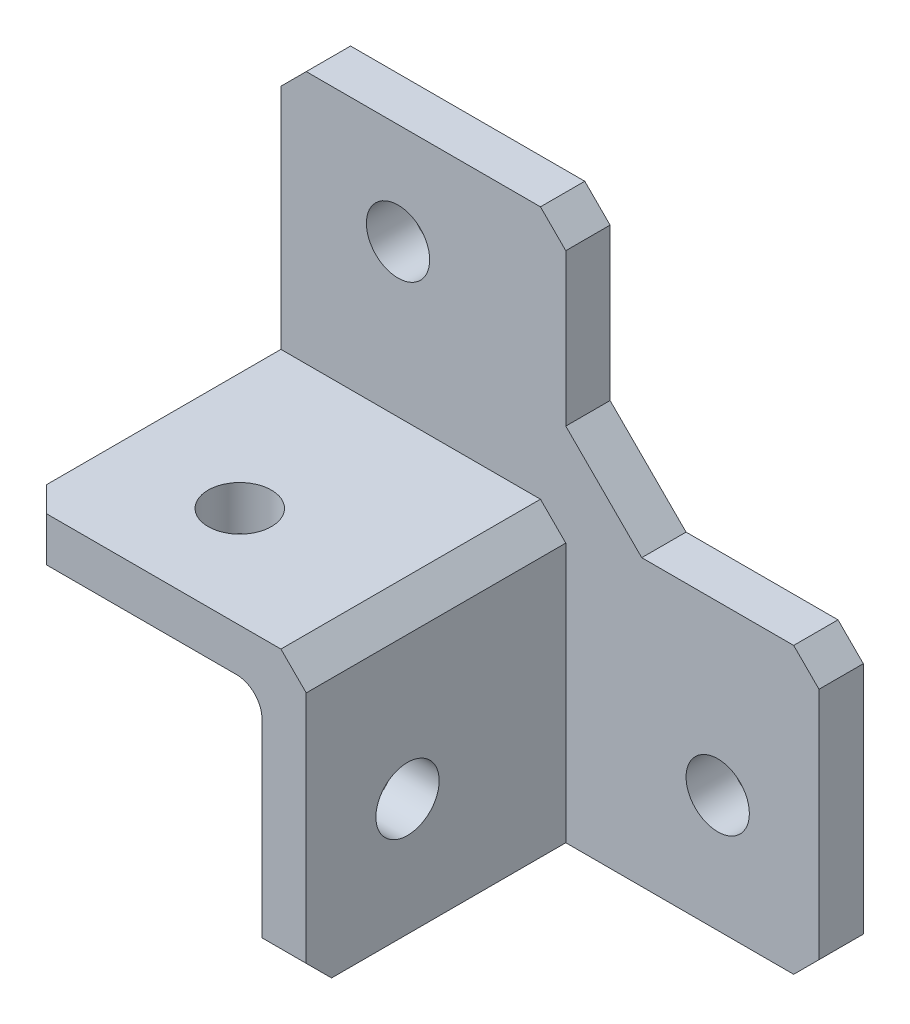
SolidWorks part; units mm, degrees
ref_plane "Plan de face" through (0, 0, 0) normal (0, 0, 1) x (1, 0, 0)
ref_plane "Plan de dessus" through (0, 0, 0) normal (0, 1, 0) x (1, 0, 0)
ref_plane "Plan de droite" through (0, 0, 0) normal (1, 0, 0) x (0, 0, -1)
sketch "Esquisse1" plane through (0, 0, 0) normal (0, 0, 1) x (1, 0, 0)
  line L0 (-26.7767, -6.3219) -> (-23.2767, -9.8219) construction
  line L1 (-45.7767, 13.6781) -> (-23.2767, 13.6781)
  line L2 (-45.7767, 13.6781) -> (-45.7767, -9.8219)
  line L3 (-45.7767, -9.8219) -> (-23.2767, -9.8219)
  line L4 (-23.2767, 13.6781) -> (-23.2767, -9.8219)
  line L5 (-26.7767, -6.3219) -> (-3.2767, -6.3219)
  line L6 (-26.7767, -6.3219) -> (-26.7767, -28.8219)
  line L7 (-26.7767, -28.8219) -> (-3.2767, -28.8219)
  line L8 (-3.2767, -6.3219) -> (-3.2767, -28.8219)
  line L9 (-23.2767, -6.3219) -> (-26.7767, -9.8219) construction
  point P8 (-26.7767, -9.8219)
  point P9 (-23.2767, -6.3219)
  dimension "D1" = 22.5
  dimension "D2" = 22.5
  dimension "D3" = 23.5
  dimension "D4" = 23.5
  dimension "D5" = 3.5
  dimension "D6" = 3.5
extrude "Boss.-Extru.1" add sketch "Esquisse1" along normal blind 3.5 contours L6 L5 L4 L1 L2 L3 | L5 L6 L3 L4 | L8 L5 L4 L3 L6 L7 region at (-34.752, 2.1652, 0) region at (-14.7895, -17.7973, 0) region at (-25.0267, -8.0719, 0)
sketch "Esquisse2" plane through (0, 0, 3.5) normal (0, 0, 1) x (1, 0, 0)
  line L1 (-45.7767, -9.8219) -> (-23.2767, -9.8219)
  line L2 (-45.7767, -9.8219) -> (-45.7767, -6.3219)
  line L3 (-45.7767, -6.3219) -> (-23.2767, -6.3219)
  line L4 (-23.2767, -9.8219) -> (-23.2767, -6.3219)
  line L5 (-26.7767, -28.8219) -> (-23.2767, -28.8219)
  line L6 (-26.7767, -28.8219) -> (-26.7767, -6.3219)
  line L7 (-26.7767, -6.3219) -> (-23.2767, -6.3219)
  line L8 (-23.2767, -28.8219) -> (-23.2767, -6.3219)
  line M1 (-45.7767, -9.8219) -> (-26.7767, -9.8219)
  line M2 (-26.7767, -9.8219) -> (-26.7767, -28.8219)
  line M3 (-26.7767, -28.8219) -> (-3.2767, -28.8219)
  line M8 (-45.7767, 13.6781) -> (-45.7767, -9.8219)
extrude "Boss.-Extru.2" add sketch "Esquisse2" along normal blind 20.5 contours L6 L3 M1 M8 | L6 L1 L4 L3 | L8 L1 M3 M2 region at (-36.2767, -8.0719, 3.5) region at (-25.0267, -8.0719, 3.5) region at (-25.0267, -19.3219, 3.5)
sketch "Esquisse3" plane through (0, -6.3219, 0) normal (0, 1, 0) x (1, 0, 0)
  line L0 (-45.7767, -24) -> (-23.2767, -24) construction
  line L1 (-23.2767, -16) -> (-45.7767, -16) construction
  line L2 (-23.2767, -24) -> (-23.2767, -3.5) construction
  line L3 (-45.7767, -24) -> (-45.7767, -3.5) construction
  circle A0 centre (-36.5267, -16) radius 2.5
  point P13 (-34.5267, -16)
  dimension "D1" = 5
  dimension "D2" = 8
  dimension "D3" = 2
extrude "Enlèv. mat.-Extru.2" cut sketch "Esquisse3" against normal blind 3.5
sketch "Esquisse4" plane through (-23.2767, 0, 0) normal (1, 0, 0) x (0, 0, -1)
  line L0 (-16, -28.8219) -> (-16, -6.3219) construction
  line L1 (-24, -28.8219) -> (-3.5, -28.8219) construction
  line L2 (-24, -6.3219) -> (-3.5, -6.3219) construction
  line L3 (-24, -28.8219) -> (-24, -6.3219) construction
  circle A0 centre (-16, -19.5719) radius 2.5
  point P10 (-16, -17.5719)
  dimension "D3" = 5
  dimension "D1" = 8
  dimension "D2" = 2
extrude "Enlèv. mat.-Extru.3" cut sketch "Esquisse4" against normal blind 3.5
sketch "Esquisse5" plane through (0, 0, 3.5) normal (0, 0, 1) x (1, 0, 0)
  line L0 (-45.7767, 5.6781) -> (-23.2767, 5.6781) construction
  line L1 (-45.7767, 13.6781) -> (-45.7767, -6.3219) construction
  line L2 (-23.2767, 13.6781) -> (-23.2767, -6.3219) construction
  line L3 (-45.7767, 13.6781) -> (-23.2767, 13.6781) construction
  circle A0 centre (-36.5267, 5.6781) radius 2.5
  point P10 (-34.5267, 5.6781)
  dimension "D2" = 5
  dimension "D1" = 8
  dimension "D3" = 2
extrude "Enlèv. mat.-Extru.4" cut sketch "Esquisse5" against normal blind 3.5
sketch "Esquisse6" plane through (0, 0, 3.5) normal (0, 0, 1) x (1, 0, 0)
  line L0 (-11.2767, -28.8219) -> (-11.2767, -6.3219) construction
  line L1 (-23.2767, -28.8219) -> (-3.2767, -28.8219) construction
  line L2 (-23.2767, -6.3219) -> (-3.2767, -6.3219) construction
  line L3 (-3.2767, -6.3219) -> (-3.2767, -28.8219) construction
  circle A0 centre (-11.2767, -19.5719) radius 2.5
  point P8 (-11.2767, -17.5719)
  dimension "D2" = 5
  dimension "D1" = 2
  dimension "D3" = 8
extrude "Enlèv. mat.-Extru.5" cut sketch "Esquisse6" against normal blind 3.5
chamfer "Chanfrein1" distance 6 angle 45 1 edges at (-23.2767, -6.3219, 1.75)
chamfer "Chanfrein2" distance 2 angle 45 1 edges at (-23.2767, -6.3219, 13.75)
chamfer "Chanfrein3" distance 2 angle 45 6 edges at (-45.7767, -8.0719, 24) (-25.0267, -28.8219, 24) (-45.7767, 13.6781, 1.75) (-3.2767, -28.8219, 1.75) (-3.2767, -6.3219, 1.75) (-23.2767, 13.6781, 1.75)
fillet "Congé1" radius 2 1 edges at (-26.7767, -9.8219, 12)
